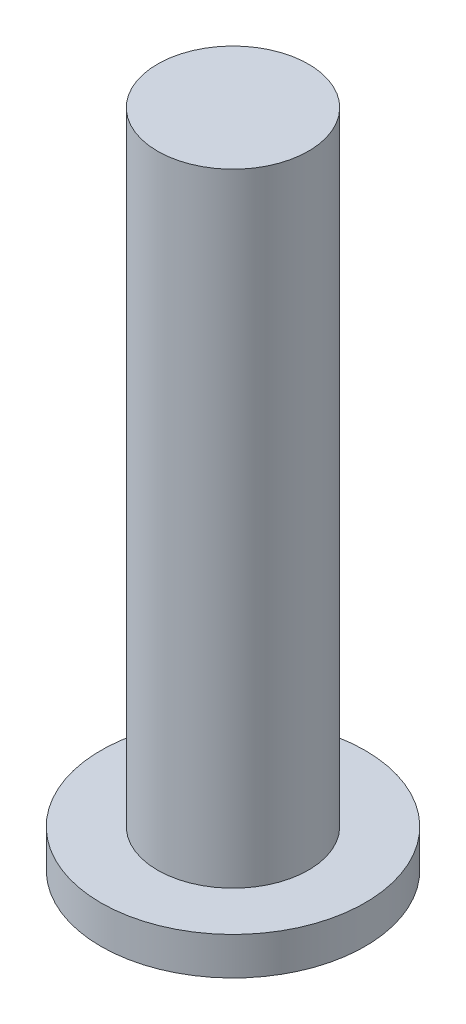
SolidWorks part; units mm, degrees
ref_plane "Plan de face" through (0, 0, 0) normal (0, 0, 1) x (1, 0, 0)
ref_plane "Plan de dessus" through (0, 0, 0) normal (0, 1, 0) x (1, 0, 0)
ref_plane "Plan de droite" through (0, 0, 0) normal (1, 0, 0) x (0, 0, -1)
sketch "Esquisse1" plane through (0, 0, 0) normal (0, 1, 0) x (1, 0, 0)
  circle A0 centre (0, 0) radius 4
  circle A1 centre (0, 0) radius 7
extrude "Boss.-Extru.1" add sketch "Esquisse1" along normal blind 2
extrude "Boss.-Extru.3" add sketch "Esquisse1<4>" along normal blind 35 contours A0
sketch "Esquisse1<4>" plane through (0, 0, 0) normal (0, 1, 0) x (1, 0, 0) same geometry as "Esquisse1"
